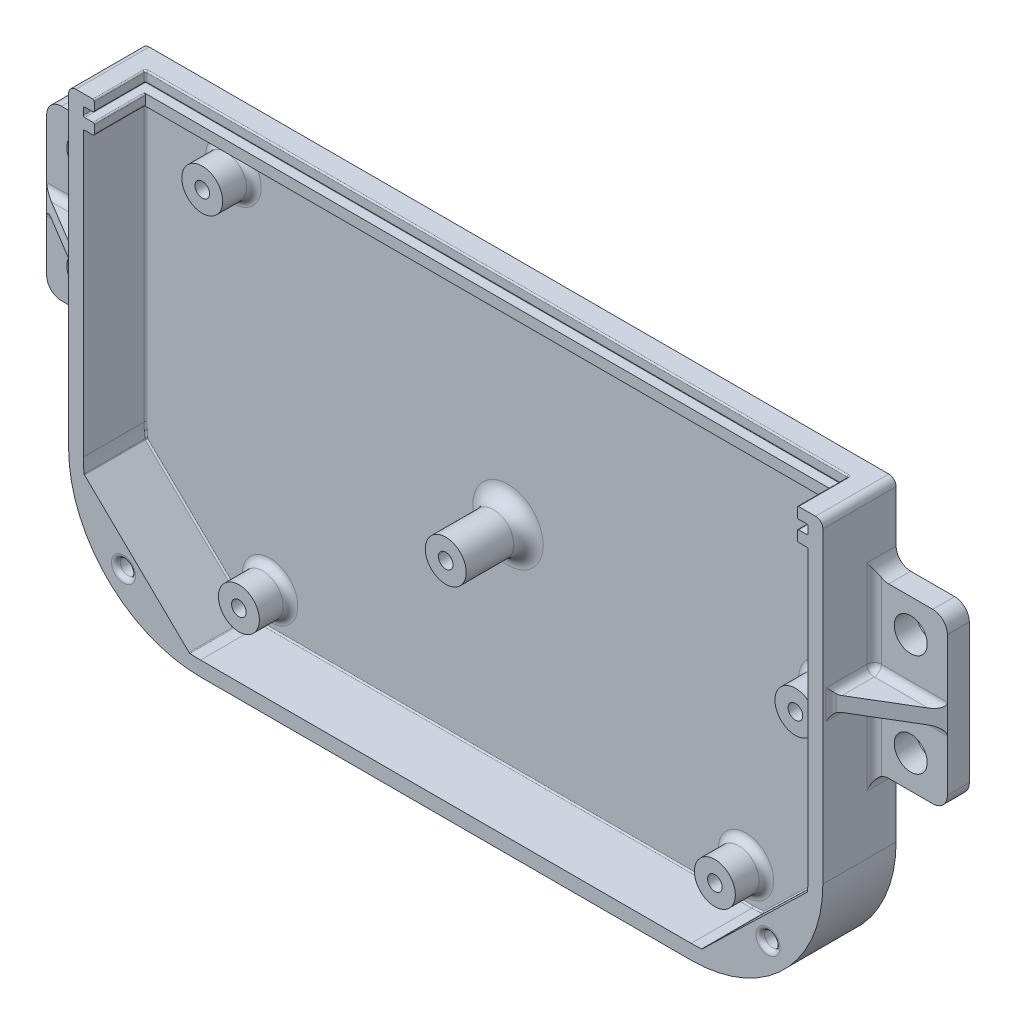
SolidWorks part; units mm, degrees
ref_plane "Plan de face" through (0, 0, 0) normal (0, 0, 1) x (1, 0, 0)
ref_plane "Plan de dessus" through (0, 0, 0) normal (0, 1, 0) x (1, 0, 0)
ref_plane "Plan de droite" through (0, 0, 0) normal (1, 0, 0) x (0, 0, -1)
sketch "Esquisse1" plane through (0, 0, 0) normal (0, 0, 1) x (1, 0, 0)
  line L1 (-50, -0.5) -> (50, -0.5) construction
  line L2 (-50, -0.5) -> (-50, 0.5) construction
  line L3 (-50, 0.5) -> (50, 0.5) construction
  line L4 (50, -0.5) -> (50, 0.5) construction
  line L5 (-50, -0.5) -> (50, 0.5) construction
  line L6 (-50, 0.5) -> (50, -0.5) construction
  line L7 (-51.5, 2) -> (51.5, 2)
  line L8 (-51.5, 2) -> (-51.5, -41)
  line L9 (-33.5, -59) -> (33.5, -59)
  line L10 (51.5, 2) -> (51.5, -41)
  arc A0 (51.5, -41) -> (33.5, -59) centre (33.5, -41) cw
  arc A1 (-33.5, -59) -> (-51.5, -41) centre (-33.5, -41) cw
  point P0 (0, 0)
  point P10 (0, 2)
  point P15 (-51.5, -59)
  dimension "D6" = 18
  dimension "D1" = 100
  dimension "D2" = 1
  dimension "D3" = 1.5
  dimension "D4" = 1.5
  dimension "D5" = 61
extrude "Boss.-Extru.1" add sketch "Esquisse1" along normal blind 10
sketch "Esquisse2" plane through (0, 0, 10) normal (0, 0, 1) x (1, 0, 0)
  line L3 (51.5, 2) -> (-51.5, 2) construction
  line L4 (-49.5, 2) -> (49.5, 2)
  line L6 (49.5, -41) -> (49.5, 2)
  line L7 (-33.5, -57) -> (33.5, -57)
  line L8 (-49.5, 2) -> (-49.5, -41)
  line L9 (49.5, -41) -> (49.5, 2)
  line L10 (-33.5, -57) -> (33.5, -57)
  line L11 (-49.5, 2) -> (-49.5, -41)
  arc A4 (33.5, -57) -> (49.5, -41) centre (33.5, -41) ccw
  arc A5 (-49.5, -41) -> (-33.5, -57) centre (-33.5, -41) ccw
  arc A6 (33.5, -57) -> (49.5, -41) centre (33.5, -41) ccw
  arc A7 (-49.5, -41) -> (-33.5, -57) centre (-33.5, -41) ccw
  dimension "D2" = 0
  dimension "D1" = 2
extrude "Enlèv. mat.-Extru.1" cut sketch "Esquisse2" against normal offset from surface (8.5 mm away) 1.5 up to face at (0, -33.9093, 0)
sketch "Esquisse3" plane through (0, 0, 1.5) normal (0, 0, 1) x (1, 0, 0)
  line L0 (49.5, -41) -> (49.5, 2) construction
  line L1 (-49.5, 2) -> (49.5, 2)
  line L2 (-49.5, 2) -> (-49.5, 0.5)
  line L3 (-49.5, 0.5) -> (49.5, 0.5)
  line L4 (49.5, 2) -> (49.5, 0.5)
  dimension "D1" = 1.5
extrude "Boss.-Extru.2" add sketch "Esquisse3" along normal blind 1.5
sketch "Esquisse4" plane through (0, 0, 1.5) normal (0, 0, 1) x (1, 0, 0)
  line L0 (-49.5, 0.5) -> (-49.5, -41) construction
  line L1 (-49.5, -0.75) -> (-48, -0.75)
  line L2 (-49.5, -0.75) -> (-49.5, -2.25)
  line L3 (-49.5, -2.25) -> (-48, -2.25)
  line L4 (-48, -0.75) -> (-48, -2.25)
  line L5 (49.5, -41) -> (49.5, 2) construction
  line L6 (49.5, -0.75) -> (48, -0.75)
  line L7 (49.5, -0.75) -> (49.5, -2.25)
  line L8 (49.5, -2.25) -> (48, -2.25)
  line L9 (48, -0.75) -> (48, -2.25)
  line L10 (-49.5, 0.5) -> (49.5, 0.5) construction
  line L11 (49.5, 2) -> (48, 2)
  line L12 (49.5, 2) -> (49.5, 0.5)
  line L13 (49.5, 0.5) -> (48, 0.5)
  line L14 (48, 2) -> (48, 0.5)
  line L16 (-49.5, 2) -> (-48, 2)
  line L17 (-49.5, 2) -> (-49.5, 0.5)
  line L18 (-49.5, 0.5) -> (-48, 0.5)
  line L19 (-48, 2) -> (-48, 0.5)
  dimension "D1" = 1.5
  dimension "D2" = 1.5
  dimension "D3" = 1.25
  dimension "D4" = 1.5
extrude "Boss.-Extru.3" add sketch "Esquisse4" along normal up to surface (8.5 mm away) up to face at (0, -33.5069, 10)
sketch "Esquisse5" plane through (0, 0, 0) normal (0, 0, -1) x (-1, 0, 0)
  line L0 (-51.5, -41) -> (-51.5, 2) construction
  line L1 (-51.5, -10) -> (-59.5, -10)
  line L2 (-51.5, -10) -> (-51.5, -35)
  line L3 (-51.5, -35) -> (-59.5, -35)
  line L4 (-59.5, -10) -> (-59.5, -35)
  line L6 (0, 0) -> (0, -67.9713) construction
  line L7 (-51.5, 2) -> (51.5, 2) construction
  line L11 (51.5, -35) -> (59.5, -35)
  line L12 (51.5, -10) -> (51.5, -35)
  line L13 (51.5, -10) -> (59.5, -10)
  line L14 (59.5, -10) -> (59.5, -35)
  line L15 (-55.5, -10) -> (-55.5, -35) construction
  circle A0 centre (-55.5, -15) radius 2.25
  circle A1 centre (-55.5, -30) radius 2.25
  circle A2 centre (55.5, -15) radius 2.25
  circle A3 centre (55.5, -30) radius 2.25
  point P8 (-59.5, -22.5)
  point P17 (-51.5, -22.5)
  point P21 (-55.5, -10)
  dimension "D3" = 4.5
  dimension "D4" = 4.5
  dimension "D1" = 8
  dimension "D2" = 25
  dimension "D5" = 7.5
  dimension "D6" = 7.5
  dimension "D7" = 12
extrude "Boss.-Extru.4" [suppressed] add sketch "Esquisse5" against normal blind 3 separate body
fillet "Congé2" [suppressed] radius 2
sketch "Esquisse6" plane through (0, 0, 0) normal (0, 0, -1) x (-1, 0, 0)
  line L0 (-51.5, -41) -> (-51.5, 2) construction
  line L1 (-51.5, -8) -> (-61.5, -8)
  line L2 (-51.5, -8) -> (-51.5, -31)
  line L3 (-51.5, -31) -> (-61.5, -31)
  line L4 (-61.5, -8) -> (-61.5, -31)
  line L5 (-51.5, 2) -> (51.5, 2) construction
  line L6 (0, 0) -> (0, -37.9918) construction
  line L7 (51.5, -8) -> (51.5, -31)
  line L8 (51.5, -31) -> (61.5, -31)
  line L9 (61.5, -8) -> (61.5, -31)
  line L10 (51.5, -8) -> (61.5, -8)
  circle A0 centre (-56.5, -12.5) radius 2.25
  circle A1 centre (-56.5, -26.5) radius 2.25
  circle A2 centre (56.5, -12.5) radius 2.25
  circle A3 centre (56.5, -26.5) radius 2.25
  point P6 (-56.5, -8)
  point P11 (-61.5, -19.5)
  dimension "D5" = 4.5
  dimension "D6" = 4.5
  dimension "D1" = 10
  dimension "D2" = 7
  dimension "D3" = 7
  dimension "D4" = 4.5
  dimension "D7" = 10
extrude "Boss.-Extru.5" add sketch "Esquisse6" against normal blind 3
fillet "Congé3" radius 2 8 edges at (51.5, -8, 1.5) (61.5, -8, 1.5) (51.5, -31, 1.5) (61.5, -31, 1.5) (-51.5, -8, 1.5) (-61.5, -8, 1.5) (-61.5, -31, 1.5) (-51.5, -31, 1.5)
fillet "Congé4" [suppressed] radius 1
fillet "Congé5" radius 1 4 edges at (-51.5, 2, 5) (51.5, -19.5, 3) (51.5, 2, 5) (-51.5, -19.5, 3)
sketch "Sketch2" plane through (0, 0, 1.5) normal (0, 0, 1) x (1, 0, 0)
  line L1 (-48, -0.75) -> (48, -0.75)
  line L2 (-48, -0.75) -> (-48, -2.25)
  line L3 (-48, -2.25) -> (48, -2.25)
  line L4 (48, -0.75) -> (48, -2.25)
extrude "Boss-Extrude1" add sketch "Sketch2" along normal up to surface (1.5 mm away) up to face at (0, 1.25, 3)
sketch "Esquisse7" plane through (0, 0, 1.5) normal (0, 0, 1) x (1, 0, 0)
  line L0 (59.5, -31) -> (53.5, -31) construction
  line L1 (0, 0) -> (0, -39.8228) construction
  line L2 (-49.3745, -43) -> (-35, -56.9295)
  line L3 (49.3745, -43) -> (35, -56.9295)
  arc A0 (35, -56.9295) -> (49.3745, -43) centre (33.5, -41) ccw
  arc A1 (33.5, -57) -> (49.5, -41) centre (33.5, -41) ccw construction
  arc A2 (33.5, -57) -> (49.5, -41) centre (33.5, -41) ccw construction
  arc A4 (-35, -56.9295) -> (-49.3745, -43) centre (-33.5, -41) cw
  dimension "D1" = 35
  dimension "D2" = 12
  dimension "D3" = 14.3745
extrude "Boss.-Extru.6" add sketch "Esquisse7" along normal up to surface (8.5 mm away) up to face at (0, -15.7565, 10)
sketch "Esquisse8" plane through (0, 0, 10) normal (0, 0, 1) x (1, 0, 0)
  line L0 (-51.5, 1) -> (-51.5, -41) construction
  line L1 (-33.5, -59) -> (33.5, -59) construction
  line L2 (0, 0) -> (0, -39.4098) construction
  circle A0 centre (-44, -51.5) radius 1.05
  circle A1 centre (44, -51.5) radius 1.05
  dimension "D3" = 2.1
  dimension "D1" = 7.5
  dimension "D2" = 7.5
extrude "Enlèv. mat.-Extru.2" cut sketch "Esquisse8" against normal blind 5
fillet "Congé6" [suppressed] radius 1
sketch "Esquisse9" plane through (0, 0, 1.5) normal (0, 0, 1) x (1, 0, 0)
  line L0 (48, 2) -> (-48, 2) construction
  line L1 (0, 2) -> (0, -59) construction
  line L2 (-33.5, -59) -> (33.5, -59) construction
  circle A0 centre (0, -28.5) radius 2.794
  point P8 (0, -28.5)
  dimension "D1" = 5.588
extrude "Boss.-Extru.7" add sketch "Esquisse9" along normal up to surface (8.5 mm away) up to face at (42.95, -51.5, 10)
fillet "Congé7" radius 2 1 edges at (-2.794, -28.5, 1.5)
sketch "Esquisse10" plane through (0, 0, 10) normal (0, 0, 1) x (1, 0, 0)
  circle A0 centre (0, -28.5) radius 0.5
  dimension "D1" = 1
extrude "Enlèv. mat.-Extru.3" cut sketch "Esquisse10" against normal blind 1
sketch "Esquisse11" plane through (0, 0, 1.5) normal (0, 0, 1) x (1, 0, 0)
  circle A0 centre (-37.5, -5.5) radius 2.794
  circle A1 centre (43.5, -26.75) radius 2.794
  circle A2 centre (-32.5, -52.5) radius 2.794
  circle A3 centre (32.5, -52.5) radius 2.794
  circle A4 centre (0, -28.5) radius 0.5 construction
  circle A5 centre (0, -28.5) radius 2.794 construction
  dimension "D1" = 5.588
  dimension "D6" = 43.5
  dimension "D9" = 23
  dimension "D10" = 1.75
  dimension "D11" = 11
  dimension "D8" = 25.75
  dimension "D5" = 37.5
  dimension "D7" = 65
extrude "Boss.-Extru.8" add sketch "Esquisse11" along normal blind 4.25
sketch "Esquisse12" plane through (0, 0, 5.75) normal (0, 0, 1) x (1, 0, 0)
  circle A0 centre (-37.5, -5.5) radius 1
  circle A1 centre (-32.5, -52.5) radius 1
  circle A2 centre (32.5, -52.5) radius 1
  circle A3 centre (43.5, -26.75) radius 1
  dimension "D4" = 2
extrude "Enlèv. mat.-Extru.4" cut sketch "Esquisse12" against normal up to surface (4.25 mm away) up to face at (-35.294, -52.5, 1.5)
fillet "Congé8" radius 1 4 edges at (-35.294, -52.5, 1.5) (29.706, -52.5, 1.5) (40.706, -26.75, 1.5) (-40.294, -5.5, 1.5)
fillet "Congé9" radius 0.6 2 edges at (42.95, -51.5, 10) (-42.95, -51.5, 10)
sketch "Esquisse14" plane through (0, -31, 0) normal (0, -1, 0) x (1, 0, 0)
  line L0 (-61.5, 3) -> (-51.5, 9)
  line L1 (-51.5, 10) -> (-51.5, 0) construction
  line L2 (-51.5, 9) -> (-51.5, 3)
  line L3 (-51.5, 4) -> (-51.5, 0) construction
  line L4 (-51.5, 3) -> (-61.5, 3)
  line L5 (0, 0) -> (0, 19.1691) construction
  line L6 (51.5, 9) -> (51.5, 3)
  line L7 (51.5, 3) -> (61.5, 3)
  line L8 (61.5, 3) -> (51.5, 9)
  dimension "D1" = 6
extrude "Boss.-Extru.9" add sketch "Esquisse14" along normal blind 2 from offset 12 offset against normal yes
fillet "Congé10" radius 1 14 edges at (51.5, -19, 6.5) (51.7929, -19, 3.2929) (51.5, -21, 6.5) (51.7929, -21, 3.2929) (-51.5, -21, 6.5) (-51.7929, -21, 3.2929) (-51.5, -19, 6.5) (-51.7929, -19, 3.2929) (57, -19, 3) (51.5, -20, 9) (57, -21, 3) (-51.5, -20, 9) (-57, -21, 3) (-57, -19, 3)
fillet "Congé11" radius 0.2 36 edges at (49.4686, -42.002, 1.5) (-34.2508, -56.9824, 1.5) (34.2508, -56.9824, 1.5) (-49.4686, -42.002, 1.5) (49.3745, -43, 5.75) (35, -56.9295, 5.75) (-35, -56.9295, 5.75) (-49.3745, -43, 5.75) (6.9788, -2.25, 1.5) (48, -2.25, 6.5) (49.5, -2.25, 5.75) (49.5, -21.625, 1.5) (42.1873, -49.9648, 1.5) (0, -57, 1.5) (-42.1873, -49.9648, 1.5) (-48, -2.25, 6.5) (-49.5, -2.25, 5.75) (-49.5, -21.625, 1.5) (-44.4788, -2.25, 1.5) (0, -0.75, 1.5) (0, 2, 3) (0, 0.5, 3) (48, 1.25, 3) (48, 2, 6.5) (48, 0.5, 6.5) (49.5, 0.5, 5.75) (49.5, -0.75, 5.75) (48, -0.75, 6.5) (-48, 2, 6.5) (-48, 1.25, 3) (-48, 0.5, 6.5) (0, 0.5, 1.5) (-49.5, 0.5, 5.75) (-49.5, -0.75, 5.75) (-48, -0.75, 6.5) (-37.4575, -2.25, 1.6607)
sketch "Sketch1" plane through (0, 0, 10) normal (0, 0, 1) x (1, 0, 0)
  circle A0 centre (0, -28.5) radius 1
  dimension "D1" = 2
extrude "Cut-Extrude1" cut sketch "Sketch1" against normal up to surface (8.5 mm away) up to face at (-36.294, -52.5, 1.5)
